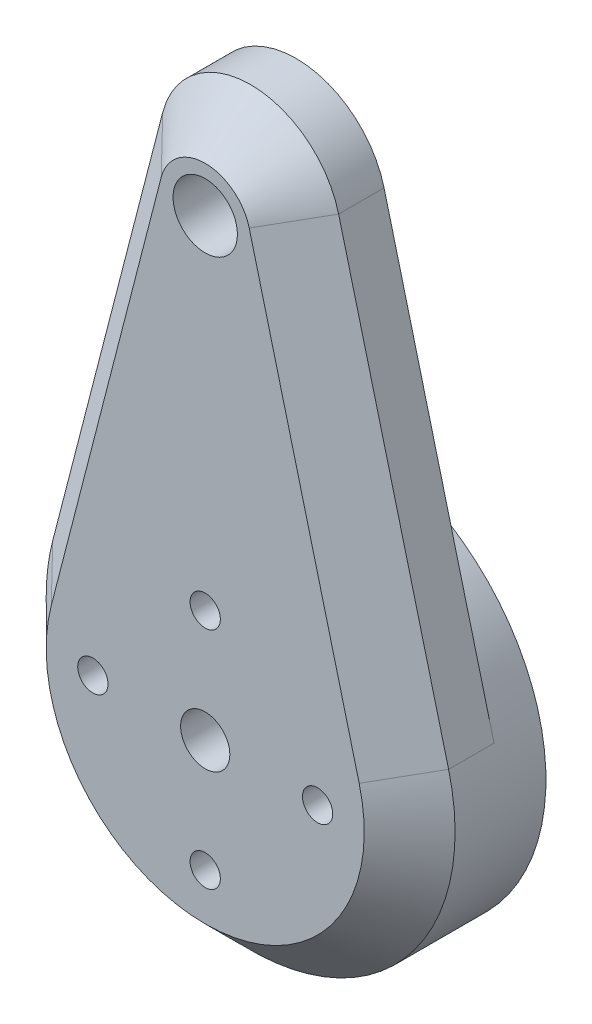
SolidWorks part; units mm, degrees
ref_plane "Front Plane" through (0, 0, 0) normal (0, 0, 1) x (1, 0, 0)
ref_plane "Top Plane" through (0, 0, 0) normal (0, 1, 0) x (1, 0, 0)
ref_plane "Right Plane" through (0, 0, 0) normal (1, 0, 0) x (0, 0, -1)
sketch "Sketch1" plane through (0, 0, 0) normal (0, 0, 1) x (1, 0, 0)
  line L0 (0, 0) -> (0, 30) construction
  line L1 (-13.0713, 3.375) -> (-5.8095, 31.5)
  line L2 (5.8095, 31.5) -> (13.0713, 3.375)
  arc A0 (-13.0713, 3.375) -> (13.0713, 3.375) centre (0, 0) ccw
  arc A1 (5.8095, 31.5) -> (-5.8095, 31.5) centre (0, 30) ccw
  circle A2 centre (0, 30) radius 2.125
  circle A3 centre (0, 0) radius 10
  circle A4 centre (0, 0) radius 1.625
  dimension "D1" = 27
  dimension "D3" = 12
  dimension "D4" = 4.25
  dimension "D5" = 20
  dimension "D6" = 3.25
  dimension "D2" = 30
extrude "Boss-Extrude1" add sketch "Sketch1" along normal blind 6 contours A3 | L2 A1 L1 A0 A3 A2 region at (0, 12.4311, 0) region at (-9.7172, 0, 0)
sketch "Sketch2" plane through (0, 0, 0) normal (0, 0, -1) x (-1, 0, 0)
  circle A0 centre (0, 0) radius 11
  dimension "D1" = 22
extrude "Cut-Extrude1" cut sketch "Sketch2" against normal blind 2
sketch "Sketch4" plane through (0, 0, 0) normal (0, 0, -1) x (-1, 0, 0)
  circle A0 centre (0, 0) radius 13.5
  circle A1 centre (0, 0) radius 11
  arc A2 (-13.0713, 3.375) -> (13.0713, 3.375) centre (0, 0) ccw construction
  circle A3 centre (0, 0) radius 11 construction
extrude "Boss-Extrude2" add sketch "Sketch4" along normal blind 3
sketch "Sketch5" plane through (0, 0, 2) normal (0, 0, -1) x (-1, 0, 0)
  line L0 (0, 0) -> (7.42, 0) construction
  circle A0 centre (7.42, 0) radius 1
  circle A1 centre (0, -7.42) radius 1
  circle A2 centre (-7.42, 0) radius 1
  circle A3 centre (0, 7.42) radius 1
  circle A4 centre (0, 0) radius 7.42 construction
  point P12 (0, 0)
  dimension "D2" = 2
  dimension "D1" = 14.84
  dimension "D3" = 4
extrude "Cut-Extrude2" cut sketch "Sketch5" against normal through all
chamfer "Chamfer1" distance 3 angle 45 4 edges at (0, -13.5, 6) (-9.4404, 17.4375, 6) (0, 36, 6) (9.4404, 17.4375, 6)
